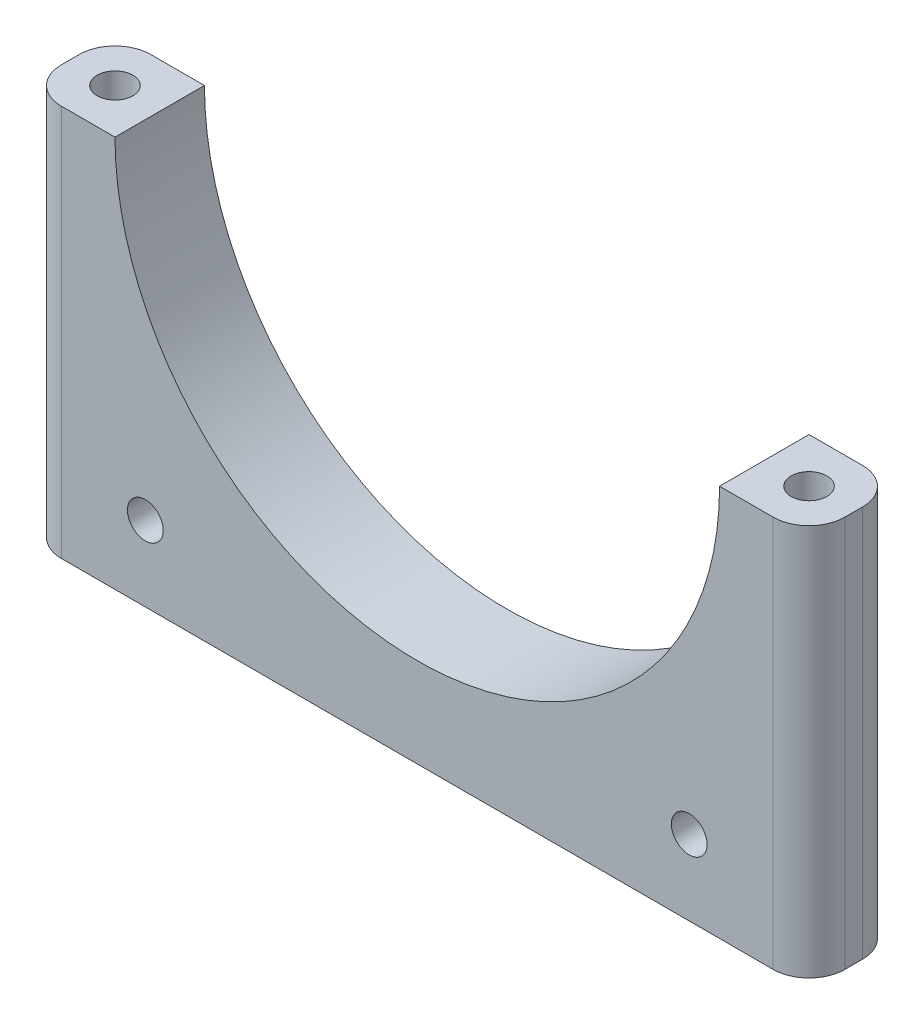
SolidWorks part; units mm, degrees
ref_plane "Front Plane" through (0, 0, 0) normal (0, 0, 1) x (1, 0, 0)
ref_plane "Top Plane" through (0, 0, 0) normal (0, 1, 0) x (1, 0, 0)
ref_plane "Right Plane" through (0, 0, 0) normal (1, 0, 0) x (0, 0, -1)
sketch "Sketch4" plane through (0, 0, 0) normal (0, 0, 1) x (1, 0, 0)
  line L0 (0, 0) -> (0, 169)
  line L1 (-84.5, 84.5) -> (84.5, 84.5)
  line L2 (0, 0) -> (0, 194)
  line L3 (-109.5, 84.5) -> (-109.5, -25)
  line L4 (109.5, 84.5) -> (109.5, -25)
  line L5 (109.5, -25) -> (0, -25)
  line L6 (0, -25) -> (-109.5, -25)
  line L7 (-109.5, 84.5) -> (109.5, 84.5)
  circle A0 centre (0, 84.5) radius 84.5
  circle A1 centre (0, 84.5) radius 109.5
  dimension "D1" = 169
  dimension "D2" = 25
extrude "Boss-Extrude1" add sketch "Sketch4" along normal blind 25 contours A1 L3 L6 | L7 A1 A0 | A1 L5 L4 region at (61.4819, 23.0181, 0) region at (-85.0412, -0.5412, 0) region at (85.0412, -0.5412, 0)
sketch "Sketch5" plane through (0, 84.5, 0) normal (0, 1, 0) x (1, 0, 0)
  line L0 (0, 0) -> (0, -33.3515) construction
  line L1 (-109.5, 0) -> (-84.5, 0) construction
  line L2 (-109.5, -25) -> (-109.5, 0) construction
  circle A0 centre (-97, -12.5) radius 5
  circle A1 centre (97, -12.5) radius 5
  dimension "D1" = 10
  dimension "D2" = 12.5
  dimension "D3" = 12.5
extrude "Cut-Extrude1" cut sketch "Sketch5" against normal blind 5000 contours A0 | A1
sketch "Sketch6" plane through (0, 0, 25) normal (0, 0, 1) x (1, 0, 0)
  line L0 (-84.5, 84.5) -> (-84.5, -25)
  line L1 (109.5, -25) -> (-109.5, -25) construction
  line L3 (0, 0) -> (0, -39.0782) construction
  line L4 (0, -4) -> (-76.015, -4) construction
  line L5 (-76.015, -4) -> (0, -4) construction
  line L6 (0, -4) -> (76.015, -4) construction
  arc A0 (-84.5, 84.5) -> (84.5, 84.5) centre (0, 84.5) ccw construction
  circle A1 centre (-76.015, -4) radius 5
  circle A2 centre (76.015, -4) radius 5
  dimension "D1" = 10
  dimension "D2" = 152.03
  dimension "D3" = 21
extrude "Cut-Extrude2" cut sketch "Sketch6" against normal blind 5000 contours A1 | A2 region at (-76.015, -4, 25) region at (76.015, -4, 25)
fillet "Fillet2" radius 10 4 edges at (109.5, 29.75, 25) (109.5, 29.75, 0) (-109.5, 29.75, 25) (-109.5, 29.75, 0)
